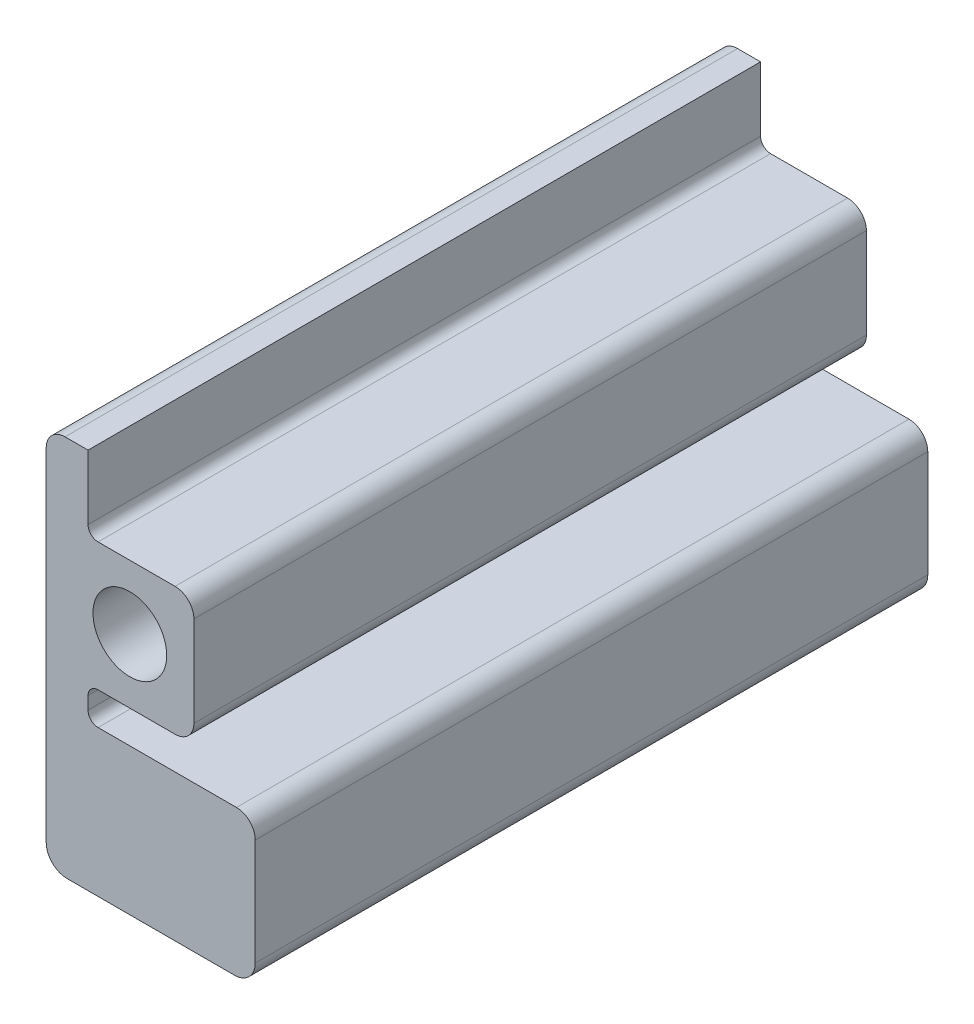
SolidWorks part; units mm, degrees
material "Pink Foam"
ref_plane "Front Plane" through (0, 0, 0) normal (0, 0, 1) x (1, 0, 0)
ref_plane "Top Plane" through (0, 0, 0) normal (0, 1, 0) x (1, 0, 0)
ref_plane "Right Plane" through (0, 0, 0) normal (1, 0, 0) x (0, 0, -1)
sketch "Sketch1" plane through (0, 0, 0) normal (0, 0, 1) x (1, 0, 0)
  line L0 (-25.4, -67.48) -> (-25.4, 36.365)
  line L2 (38.1, -67.48) -> (38.1, -35.095)
  line L3 (32.385, -29.38) -> (-9.652, -29.38)
  line L4 (-12.7, -26.332) -> (-12.7, -22.503)
  line L5 (-9.652, -19.455) -> (0, -19.455)
  line L6 (-9.652, 19.455) -> (0, 19.455)
  line L7 (-12.7, 22.503) -> (-12.7, 26.332)
  line L8 (-9.652, 29.38) -> (32.385, 29.38)
  line L9 (38.1, 35.095) -> (38.1, 36.365)
  line L10 (32.385, 42.08) -> (-19.685, 42.08)
  line L15 (0, -11.2) -> (0, -19.455) construction
  line L16 (0, 11.2) -> (0, 19.455) construction
  line L17 (11.2, 0) -> (19.455, 0) construction
  line L18 (0, 19.455) -> (13.74, 19.455)
  line L19 (19.455, 13.74) -> (19.455, 0)
  line L20 (19.455, 0) -> (19.455, -13.74)
  line L21 (13.74, -19.455) -> (0, -19.455)
  line L24 (31.75, -73.83) -> (-19.05, -73.83)
  circle A0 centre (0, 0) radius 11.2
  arc A3 (-19.685, 42.08) -> (-25.4, 36.365) centre (-19.685, 36.365) ccw
  arc A4 (38.1, 36.365) -> (32.385, 42.08) centre (32.385, 36.365) ccw
  arc A6 (32.385, 29.38) -> (38.1, 35.095) centre (32.385, 35.095) ccw
  arc A7 (38.1, -35.095) -> (32.385, -29.38) centre (32.385, -35.095) ccw
  arc A8 (19.455, -13.74) -> (13.74, -19.455) centre (13.74, -13.74) cw
  arc A9 (13.74, 19.455) -> (19.455, 13.74) centre (13.74, 13.74) cw
  arc A10 (-12.7, 26.332) -> (-9.652, 29.38) centre (-9.652, 26.332) cw
  arc A11 (-9.652, 19.455) -> (-12.7, 22.503) centre (-9.652, 22.503) cw
  arc A12 (-12.7, -22.503) -> (-9.652, -19.455) centre (-9.652, -22.503) cw
  arc A13 (-9.652, -29.38) -> (-12.7, -26.332) centre (-9.652, -26.332) cw
  arc A14 (31.75, -73.83) -> (38.1, -67.48) centre (31.75, -67.48) ccw
  arc A15 (-19.05, -73.83) -> (-25.4, -67.48) centre (-19.05, -67.48) cw
  point P12 (0, 11.2)
  point P20 (0, -11.2)
  point P22 (11.2, 0)
  point P45 (-12.7, 29.38)
  point P48 (-12.7, 19.455)
  point P53 (-12.7, -29.38)
  point P57 (38.1, -73.83)
  point P60 (38.1, -73.83)
  point P63 (-25.4, -73.83)
  dimension "D1" = 22.4
  dimension "D11" = 3.048
  dimension "D9" = 5.715
  dimension "D14" = 5.715
  dimension "D12" = 6.35
  dimension "D2" = 25.4
  dimension "D3" = 8.255
  dimension "D4" = 9.925
  dimension "D5" = 44.45
  dimension "D6" = 9.925
  dimension "D7" = 12.7
  dimension "D8" = 12.7
  dimension "D10" = 63.5
extrude "Boss-Extrude1" add sketch "Sketch1" along normal blind 204.3137
sketch "Sketch2" plane through (0, 0, 204.3137) normal (0, 0, 1) x (1, 0, 0)
  line L0 (38.1, 35.095) -> (38.1, 36.365) construction
  line L1 (19.455, -13.74) -> (38.1, -13.74)
  line L2 (19.455, -13.74) -> (19.455, 42.08)
  line L3 (19.455, 42.08) -> (38.1, 42.08)
  line L4 (38.1, -13.74) -> (38.1, 42.08)
  line L5 (32.385, 42.08) -> (-19.685, 42.08) construction
  line L7 (-12.7, 22.503) -> (19.455, 22.503)
  line L8 (-12.7, 22.503) -> (-12.7, 42.08)
  line L9 (-12.7, 42.08) -> (19.455, 42.08)
  line L10 (19.455, 22.503) -> (19.455, 42.08)
  line M7 (19.455, -13.74) -> (19.455, 13.74)
  line M11 (-12.7, 22.503) -> (-12.7, 26.332)
  arc M12 (-12.7, 26.332) -> (-9.652, 29.38) centre (-9.652, 26.332) cw
  line M13 (-9.652, 29.38) -> (32.385, 29.38)
  arc M14 (32.385, 29.38) -> (38.1, 35.095) centre (32.385, 35.095) ccw
  line M15 (38.1, 35.095) -> (38.1, 36.365)
  arc M16 (38.1, 36.365) -> (32.385, 42.08) centre (32.385, 36.365) ccw
  line M17 (32.385, 42.08) -> (-19.685, 42.08)
extrude "Cut-Extrude1" cut sketch "Sketch2" against normal blind 236.982 contours L2 M13 M14 M15 M16 M17 | L8 L2 M12 M13 M17 | L1 L4 L2 M14 M13 M7 | L4 L3 M16 | L7 L2 M11 M13 M12 region at (28.847, 8.0174, 204.3137) region at (28.2712, 35.73, 204.3137) region at (3.5176, 25.9164, 204.3137) region at (36.8235, 40.8035, 204.3137) region at (3.3027, 35.6958, 204.3137)
